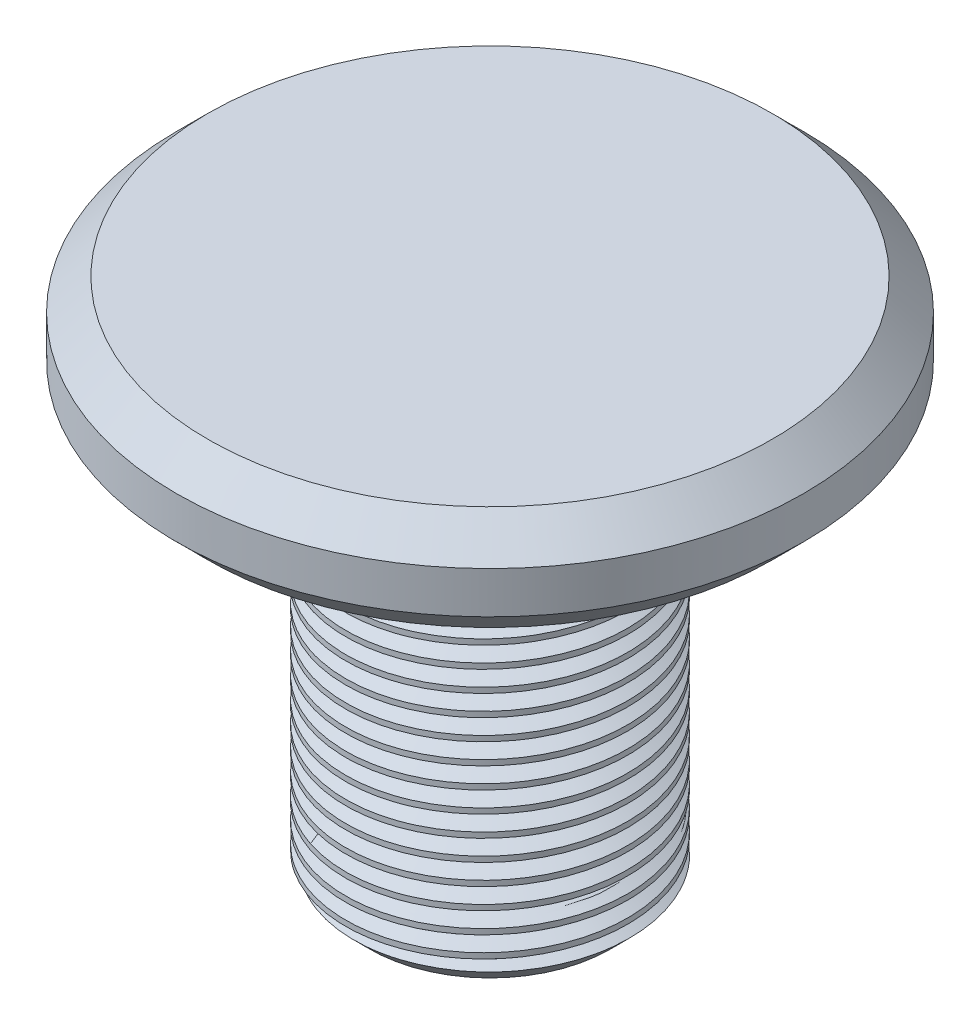
SolidWorks part; units mm, degrees
ref_plane "前基準面" through (0, 0, 0) normal (0, 0, 1) x (1, 0, 0)
ref_plane "上基準面" through (0, 0, 0) normal (0, 1, 0) x (1, 0, 0)
ref_plane "右基準面" through (0, 0, 0) normal (1, 0, 0) x (0, 0, -1)
sketch "草圖1" plane through (0, 0, 0) normal (0, 0, 1) x (1, 0, 0)
  line L0 (0, -1000) -> (0, 49000) construction
  line L1 (0, 0) -> (30, 0)
  line L2 (30, 0) -> (30, -10)
  line L3 (30, -10) -> (13.5, -10)
  line L4 (13.5, -10) -> (13.5, -50)
  line L5 (13.5, -50) -> (0, -50)
  line L6 (0, -50) -> (0, 0)
  dimension "D1" = 60
  dimension "D2" = 27
  dimension "D3" = 10
  dimension "D4" = 40
revolve "旋轉1" add sketch "草圖1" angle 360 about L0
chamfer "導角1" distance 3 angle 45 2 edges at (30, -10, 0) (30, 0, 0)
chamfer "導角2" distance 2 angle 45 1 edges at (13.5, -50, 0)
sketch "草圖2" plane through (0, -50, 0) normal (0, -1, 0) x (1, 0, 0)
  circle A0 centre (0, 0) radius 13.5
curve "螺旋曲線/渦捲線1" pitch 2 height 40 turns 20
sketch "草圖3" plane through (0, 0, 0) normal (1, 0, 0) x (0, 0, -1)
  line L0 (-13.52, -35.3897) -> (-13.52, -59.7559) construction
  line L1 (-1000, -50) -> (49000, -50) construction
  line L2 (-11.5, -50) -> (11.5, -50) construction
  line L3 (-13.5, -10) -> (-13.5, -48) construction
  line L4 (-13.52, -49.25) -> (-12.221, -50)
  line L5 (-12.221, -50) -> (-13.52, -50.75)
  line L6 (-13.52, -50.75) -> (-13.52, -49.25)
  point P7 (0, -50)
  dimension "D1" = 0.02
  dimension "D2" = 60
  dimension "D3" = 1.299
sweep "除料-掃出1" cut profiles "草圖3" path "螺旋曲線/渦捲線1"
